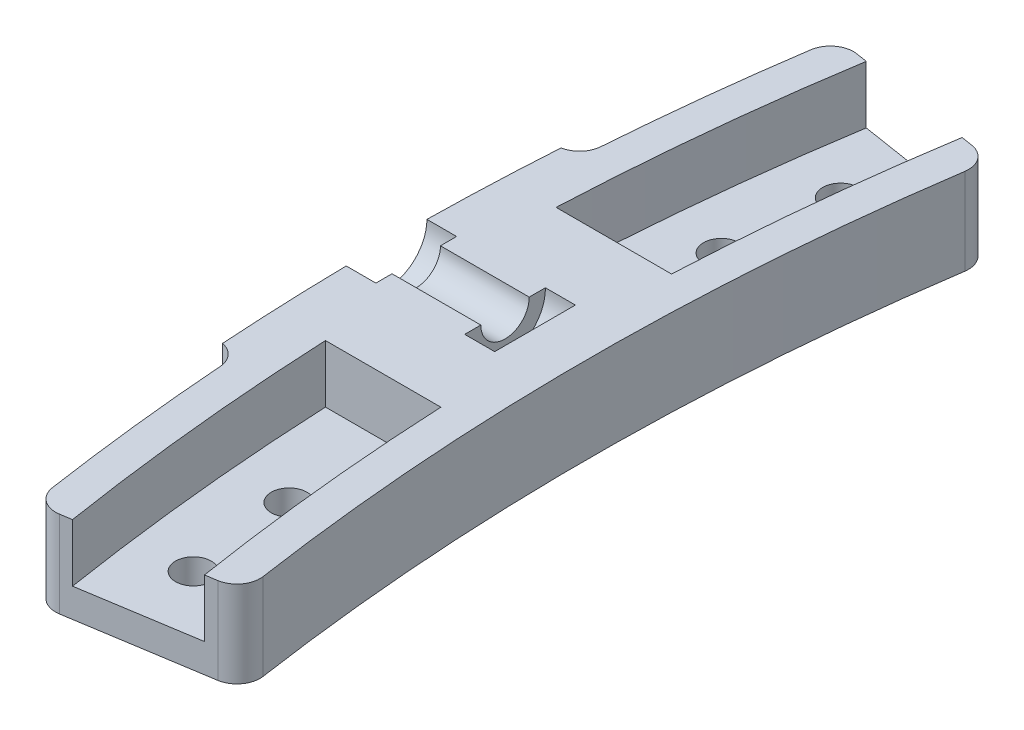
SolidWorks part; units mm, degrees
ref_plane "Front Plane" through (0, 0, 0) normal (0, 0, 1) x (1, 0, 0)
ref_plane "Top Plane" through (0, 0, 0) normal (0, 1, 0) x (1, 0, 0)
ref_plane "Right Plane" through (0, 0, 0) normal (1, 0, 0) x (0, 0, -1)
sketch "Sketch1" plane through (0, 0, 0) normal (0, 1, 0) x (1, 0, 0)
  line L0 (0, 0) -> (-217.2914, -34.4156) construction
  line L1 (0, 0) -> (-217.2914, 34.4156) construction
  line L2 (0, 0) -> (-215, 0) construction
  line L3 (-217.2914, 34.4156) -> (-207.4146, 32.8512)
  line L4 (-207.4146, -32.8512) -> (-217.2914, -34.4156)
  line L5 (0, 0) -> (-220.2545, -34.8849) construction
  line L6 (0, 0) -> (-220.2545, 34.8849) construction
  line L7 (-220.2545, 34.8849) -> (-204.4515, 32.3819)
  line L8 (-220.2545, -34.8849) -> (-204.4515, -32.3819)
  arc A0 (-217.2914, 34.4156) -> (-217.2914, -34.4156) centre (0, 0) ccw
  arc A1 (-207.4146, 32.8512) -> (-207.4146, -32.8512) centre (0, 0) ccw
  arc A2 (-212.353, -33.6334) -> (-212.353, 33.6334) centre (0, 0) cw construction
  arc A4 (-204.4515, 32.3819) -> (-204.4515, -32.3819) centre (0, 0) ccw
  arc A5 (-220.2545, 34.8849) -> (-220.2545, -34.8849) centre (0, 0) ccw
  dimension "D1" = 220
  dimension "D2" = 210
  dimension "D3" = 5
  dimension "D5" = 207
  dimension "D6" = 223
  dimension "D4" = 18
extrude "Boss-Extrude1" add sketch "Sketch1" along normal blind 7.5 contours A1 L3 A0 L4 | L7 A5 L8 A0 | A4 L7 A1 L8
ref_plane "Plane1" through (-215, 0, 0) normal (1, 0, 0) x (0, 0, -1)
sketch "Sketch19" plane through (0, 0, 0) normal (0, 1, 0) x (1, 0, 0)
  line L0 (0, 0) -> (-224.0193, 14.683) construction
  line L1 (0, 0) -> (-224.0193, -14.683) construction
  line L4 (0, 0) -> (-224.5, 0) construction
  line L5 (-224.0193, 14.683) -> (-222.5225, 14.5849)
  line L6 (-224.0193, -14.683) -> (-222.5225, -14.5849)
  arc A0 (-224.0193, 14.683) -> (-224.0193, -14.683) centre (0, 0) ccw
  arc A1 (-220.2545, 34.8849) -> (-220.2545, -34.8849) centre (0, 0) ccw construction
  arc A2 (-222.5225, 14.5849) -> (-222.5225, -14.5849) centre (0, 0) ccw
  dimension "D1" = 224.5
  dimension "D2" = 3.75
extrude "Boss-Extrude2" add sketch "Sketch19" along normal blind 7.5
sketch "Sketch15" plane through (0, 7.5, 0) normal (0, 1, 0) x (1, 0, 0)
  line L0 (-207.4146, -32.8512) -> (-217.2914, -34.4156) construction
  line L1 (-205, 10) -> (-225, 10)
  line L2 (-205, 10) -> (-205, -10)
  line L3 (-205, -10) -> (-225, -10)
  line L4 (-225, 10) -> (-225, -10)
  line L5 (-205, 10) -> (-225, -10) construction
  line L6 (-205, -10) -> (-225, 10) construction
  line L7 (-217.2914, 34.4156) -> (-207.4146, 32.8512) construction
  line L8 (-207.4146, -32.8512) -> (-217.2914, -34.4156)
  line L9 (-217.2914, 34.4156) -> (-207.4146, 32.8512)
  arc A2 (-207.4146, 32.8512) -> (-207.4146, -32.8512) centre (0, 0) ccw construction
  arc A3 (-217.2914, 34.4156) -> (-217.2914, -34.4156) centre (0, 0) ccw construction
  arc A4 (-207.4146, 32.8512) -> (-207.4146, -32.8512) centre (0, 0) ccw
  arc A5 (-217.2914, 34.4156) -> (-217.2914, -34.4156) centre (0, 0) ccw
  point P0 (-215, 0)
  line M5 (-220.2545, -34.8849) -> (-204.4515, -32.3819)
  line M7 (-204.4515, 32.3819) -> (-220.2545, 34.8849)
  dimension "D1" = 20
  dimension "D2" = 20
extrude "Cut-Extrude1" cut sketch "Sketch15" against normal blind 5 contours A5 L1 A4 M7 | L3 A5 A4 M5
ref_plane "Plane2" through (-215, 0, 0) normal (-1, 0, 0) x (0, 0, 1)
sketch "Sketch12" plane through (0, 0, 0) normal (0, 1, 0) x (1, 0, 0)
  line L0 (0, 0) -> (-214.1819, -18.7385) construction
  line L1 (0, 0) -> (-213.1606, -28.0631) construction
  line L2 (0, 0) -> (-215, 0) construction
  line L3 (0, 0) -> (-215, 0) construction
  line L4 (0, 0) -> (-214.1819, 18.7385) construction
  line L5 (0, 0) -> (-213.1606, 28.0631) construction
  arc A0 (-212.353, 33.6334) -> (-212.353, -33.6334) centre (0, 0) ccw construction
  dimension "D1" = 10
  dimension "D2" = 15
hole_wizard "Ø3.1 (3.1) Diameter Hole2" positions "Sketch18" profile "Sketch17" hole size "Ø3.1" standard "ISO" end condition through all
sketch "Sketch18" plane through (0, 0, 0) normal (0, -1, 0) x (-1, 0, 0)
  point P0 (213.1606, -28.0631)
  point P3 (214.1819, -18.7385)
  point P6 (214.1819, 18.7385)
  point P9 (213.1606, 28.0631)
sketch "Sketch17" plane through (-213.1606, 0, 28.0631) normal (1, 0, 0) x (0, 0, -1)
  line L0 (0, 0) -> (0, 7.5)
  line L1 (0, 7.5) -> (1.55, 7.5)
  line L2 (1.55, 7.5) -> (1.55, 0)
  line L5 (1.55, 0) -> (0, 0)
  line L11 (0, -6.35) -> (0, 107.95) construction
  dimension "Thru Hole Dia." = 3.1
  dimension "Thru Hole Depth" = 7.5
sketch "Sketch20" plane through (0, 0, 0) normal (0, 1, 0) x (1, 0, 0)
  line L0 (-205, 0) -> (-192.5, 0) construction
  line L1 (0, 0) -> (-205, 0) construction
  arc A2 (-224.0193, 14.683) -> (-224.0193, -14.683) centre (0, 0) ccw construction
  point P3 (-224.5, 0)
  dimension "D1" = 205
  dimension "D2" = 12.5
ref_plane "Plane3" through (-192.5, 0, 0) normal (1, 0, 0) x (0, 0, -1)
ref_plane "Plane4" through (-224.5, 0, 0) normal (1, 0, 0) x (0, 0, -1)
fillet "Fillet1" radius 2 4 edges at (-220.2545, 3.75, -34.8849) (-204.4515, 3.75, -32.3819) (-204.4515, 3.75, 32.3819) (-220.2545, 3.75, 34.8849)
fillet "Fillet2" radius 2 2 edges at (-222.5225, 3.75, -14.5849) (-222.5225, 3.75, 14.5849)
sketch "Sketch21" plane through (0, 7.5, 0) normal (0, 1, 0) x (1, 0, 0)
  line L0 (-225, 0) -> (0, 0) construction
  line L1 (-225, 0) -> (-212.5, 0) construction
  dimension "D1" = 225
  dimension "D2" = 12.5
ref_plane "Plane5" through (-212.5, 0, 0) normal (1, 0, 0) x (0, 0, -1)
sketch "Sketch22" plane through (-212.5, 0, 0) normal (1, 0, 0) x (0, 0, -1)
  line L0 (30.424, 7.5) -> (-30.424, 7.5) construction
  circle A0 centre (0, 7.5) radius 2.1
  dimension "D1" = 4.2
extrude "Cut-Extrude2" cut sketch "Sketch22" against normal through all and the other way up to surface (0.9 mm away)
sketch "Sketch23" plane through (-211.6, 0, 0) normal (-1, 0, 0) x (0, 0, 1)
  circle A0 centre (0, 7.4392) radius 3.5
  dimension "D1" = 7
extrude "Cut-Extrude3" cut sketch "Sketch23" along normal blind 2.6
sketch "Sketch24" plane through (0, 7.5, 0) normal (0, 1, 0) x (1, 0, 0)
  line L0 (-224.5, 0) -> (-207, 0) construction
  line L2 (-224.5, 0) -> (-221.9, 0)
  line L3 (-224.5, 0) -> (-224.5, 3.5)
  line L4 (-224.5, 3.5) -> (-221.9, 3.5)
  line L5 (-221.9, 0) -> (-221.9, 3.5)
  arc A0 (-224.4902, 2.1) -> (-224.4902, -2.1) centre (0, 0) ccw construction
  arc A1 (-204.752, 30.424) -> (-204.752, -30.424) centre (0, 0) ccw construction
  dimension "D1" = 2.6
  dimension "D2" = 7
revolve "Cut-Revolve1" cut sketch "Sketch24" angle 360 about L0
